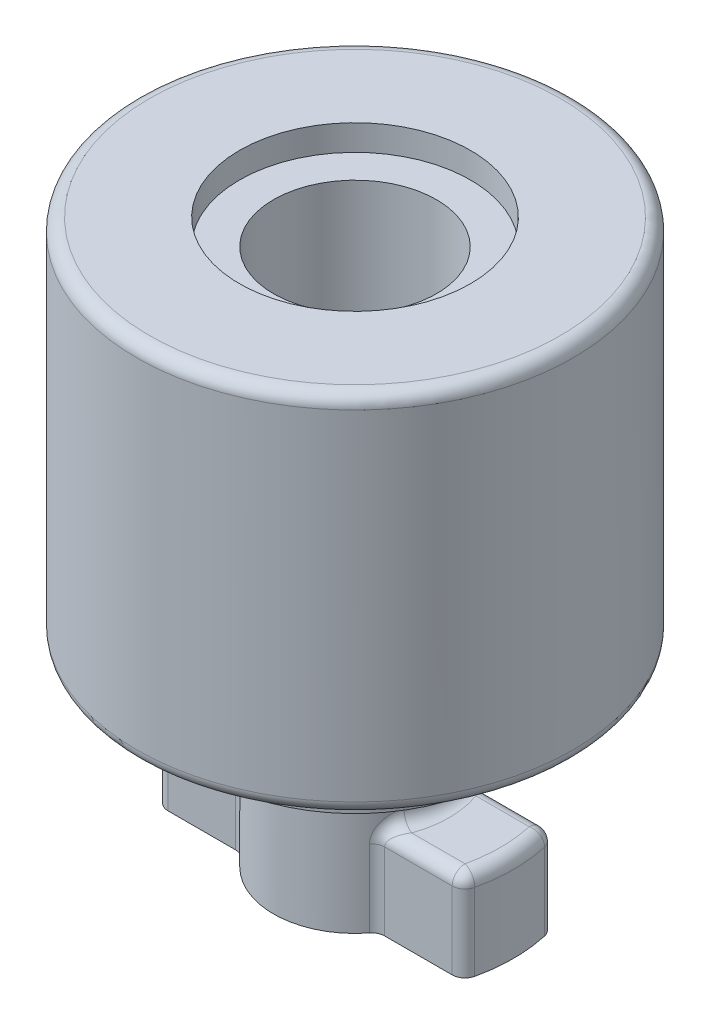
SolidWorks part; units mm, degrees
ref_plane "CL Y" through (0, 0, 0) normal (0, 0, 1) x (1, 0, 0)
ref_plane "Bottom" through (0, 0, 0) normal (0, 1, 0) x (1, 0, 0)
ref_plane "CL X " through (0, 0, 0) normal (1, 0, 0) x (0, 0, -1)
sketch "Sketch1" plane through (0, 0, 0) normal (0, 0, 1) x (1, 0, 0)
  line L0 (-8.5, 14.22) -> (-3.175, 14.22)
  line L1 (0, -50) -> (0, 50) construction
  line L2 (-8.5, 14.22) -> (-8.5, 0)
  line L3 (50, 0) -> (-50, 0) construction
  line L4 (-8.5, 0) -> (-5.66, 0)
  line L5 (-5.66, 0) -> (-5.66, -1.9)
  line L6 (-5.66, -1.9) -> (-3.175, -1.9)
  line L7 (-3.175, -1.9) -> (-3.175, -7.7)
  line L8 (-3.175, -7.7) -> (0, -7.7)
  line L9 (0, 3.04) -> (0, -7.7) construction
  line L10 (-6.7, -1.3) -> (-6.7, -4.2297) construction
  line L11 (-6.7, -1.3) -> (-5.39, -1.3) construction
  line L12 (-6.7, -2.61) -> (-5.1144, -2.61) construction
  line L13 (-9.3715, -2.4) -> (0.6009, -2.4) construction
  line L14 (-8.1323, -4.7) -> (4.6223, -4.7) construction
  line L15 (0, 3.04) -> (0, -7.7)
  line L16 (-3.175, 14.22) -> (-3.175, 3.04)
  line L17 (-3.175, 3.04) -> (0, 3.04)
  circle A0 centre (-6.7, -1.3) radius 1.31 construction
  dimension "D7" = 2.62
  dimension "D2" = 14.22
  dimension "D3" = 1.9
  dimension "D4" = 5.66
  dimension "D5" = 6.7
  dimension "D6" = 1.3
  dimension "D8" = 5.39
  dimension "D9" = 0.5
  dimension "D10" = 6.35
  dimension "D11" = 2.3
  dimension "D12" = 3
  dimension "D13" = 8.5
  dimension "11.18" = 11.18
  dimension "D14" = 3.175
revolve "Revolve1" add sketch "Sketch1" angle 360 about L15
sketch "Sketch2" plane through (0, -7.7, 0) normal (0, -1, 0) x (1, 0, 0)
  line L0 (-3.175, 0) -> (3.175, 0) construction
  line L1 (-6.175, 0) -> (6.175, 0) construction
  line L2 (-5.9218, 1.75) -> (5.9218, 1.75)
  line L3 (0, 1.75) -> (0, -1.75) construction
  line L4 (-5.9218, -1.75) -> (5.9218, -1.75)
  circle A0 centre (0, 0) radius 3.175 construction
  circle A1 centre (0, 0) radius 3.175 construction
  arc A2 (-5.9218, 1.75) -> (-5.9218, -1.75) centre (0, 0) ccw
  arc A3 (5.9218, -1.75) -> (5.9218, 1.75) centre (0, 0) ccw
  dimension "D4" = 1.75
  dimension "D5" = 6.175
  dimension "D1" = 3
  dimension "D2" = 3
  dimension "D3" = 1.75
extrude "Boss-Extrude1" add sketch "Sketch2" against normal blind 3.5
fillet "Fillet1" radius 1.2 1 edges at (-5.66, 0, 0)
fillet "Fillet2" radius 0.5 18 edges at (2.6492, -5.95, 1.75) (3.175, -4.2, 0) (-2.6492, -5.95, -1.75) (-2.6492, -5.95, 1.75) (-8.5, 14.22, 0) (-8.5, 0, 0) (6.175, -4.2, 0) (5.9218, -5.95, -1.75) (4.2855, -4.2, -1.75) (2.6492, -5.95, -1.75) (-4.2855, -4.2, -1.75) (-5.9218, -5.95, -1.75) (-6.175, -4.2, 0) (4.2855, -4.2, 1.75) (-4.2855, -4.2, 1.75) (5.9218, -5.95, 1.75) (-5.9218, -5.95, 1.75) (-3.175, -4.2, 0)
sketch "Sketch4" plane through (0, 14.22, 0) normal (0, 1, 0) x (1, 0, 0)
  circle A0 centre (0, 0) radius 4.5
  dimension "D1" = 9
extrude "Cut-Extrude1" cut sketch "Sketch4" against normal blind 1
